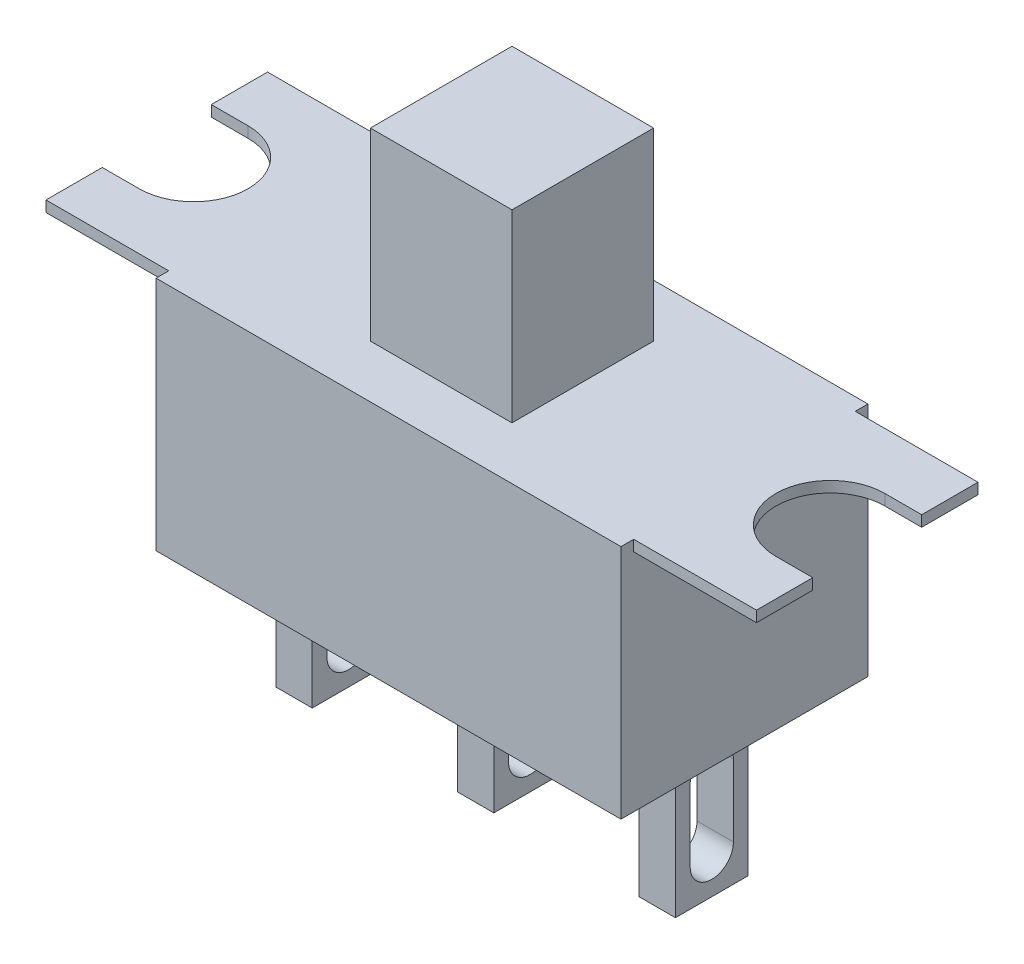
SolidWorks part; units mm, degrees
ref_plane "Front" through (0, 0, 0) normal (0, 0, 1) x (1, 0, 0)
ref_plane "Top" through (0, 0, 0) normal (0, 1, 0) x (1, 0, 0)
ref_plane "Side" through (0, 0, 0) normal (1, 0, 0) x (0, 0, -1)
ref_axis "X_Axis" through (-20.1896, 0, 0) along (1, 0, 0)
ref_axis "Y_Axis" through (0, -14.8261, 0) along (0, 1, 0)
ref_axis "Z_Axis" through (0, 0, -19.842) along (0, 0, 1)
sketch "Sketch1" plane through (0, 0, 0) normal (0, 1, 0) x (1, 0, 0)
  line L1 (6.4, 3.4) -> (-6.4, 3.4)
  line L2 (6.4, 3.4) -> (6.4, -3.4)
  line L3 (6.4, -3.4) -> (-6.4, -3.4)
  line L4 (-6.4, 3.4) -> (-6.4, -3.4)
  line L5 (6.4, 3.4) -> (-6.4, -3.4) construction
  line L6 (6.4, -3.4) -> (-6.4, 3.4) construction
  point P0 (0, 0)
  dimension "D1" = 6.8
  dimension "D2" = 12.8
extrude "Boss-Extrude1" add sketch "Sketch1" along normal blind 6.5
sketch "Sketch2" plane through (0, 6.5, 0) normal (0, 1, 0) x (1, 0, 0)
  line L0 (0, 3.05) -> (0, -3.05) construction
  line L1 (9.78, 3.05) -> (-9.78, 3.05)
  line L2 (9.78, 3.05) -> (9.78, 1.5)
  line L3 (9.78, -3.05) -> (-9.78, -3.05)
  line L4 (-9.78, 3.05) -> (-9.78, 1.5)
  line L5 (9.78, 3.05) -> (-9.78, -3.05) construction
  line L6 (9.78, -3.05) -> (-9.78, 3.05) construction
  line L7 (-8.765, 1.5) -> (-9.78, 1.5)
  line L9 (-9.78, -1.5) -> (-8.765, -1.5)
  line L10 (8.765, 1.5) -> (9.78, 1.5)
  line L12 (9.78, -1.5) -> (8.765, -1.5)
  line L13 (-9.78, -1.5) -> (-9.78, -3.05)
  line L14 (9.78, -1.5) -> (9.78, -3.05)
  arc A0 (-8.765, -1.5) -> (-8.765, 1.5) centre (-8.765, 0) ccw
  arc A1 (8.765, 1.5) -> (8.765, -1.5) centre (8.765, 0) ccw
  point P0 (0, 0)
  point P18 (8.765, 0.2525)
  dimension "D3" = 3
  dimension "D1" = 6.1
  dimension "D2" = 19.56
  dimension "D4" = 17.53
extrude "Boss-Extrude2" add sketch "Sketch2" against normal blind 0.3
sketch "Sketch3" plane through (0, 6.5, 0) normal (0, 1, 0) x (1, 0, 0)
  line L1 (1.95, 1.95) -> (-1.95, 1.95)
  line L2 (1.95, 1.95) -> (1.95, -1.95)
  line L3 (1.95, -1.95) -> (-1.95, -1.95)
  line L4 (-1.95, 1.95) -> (-1.95, -1.95)
  line L5 (1.95, 1.95) -> (-1.95, -1.95) construction
  line L6 (1.95, -1.95) -> (-1.95, 1.95) construction
  point P0 (0, 0)
  dimension "D1" = 3.9
  dimension "D2" = 3.9
extrude "Boss-Extrude3" add sketch "Sketch3" along normal blind 5.08
sketch "Sketch4" plane through (0, 0, 0) normal (0, -1, 0) x (1, 0, 0)
  line L0 (-6.4, 0) -> (6.4, 0) construction
  line L1 (-0.5, 1) -> (0.5, 1)
  line L2 (-0.5, 1) -> (-0.5, -1)
  line L3 (-0.5, -1) -> (0.5, -1)
  line L4 (0.5, 1) -> (0.5, -1)
  line L5 (-0.5, 1) -> (0.5, -1) construction
  line L6 (-0.5, -1) -> (0.5, 1) construction
  line L7 (4.5, 1) -> (5.5, 1)
  line L8 (4.5, 1) -> (4.5, -1)
  line L9 (4.5, -1) -> (5.5, -1)
  line L10 (5.5, 1) -> (5.5, -1)
  line L11 (4.5, 1) -> (5.5, -1) construction
  line L12 (4.5, -1) -> (5.5, 1) construction
  line L13 (-5.5, 1) -> (-4.5, 1)
  line L14 (-5.5, 1) -> (-5.5, -1)
  line L15 (-5.5, -1) -> (-4.5, -1)
  line L16 (-4.5, 1) -> (-4.5, -1)
  line L17 (-5.5, 1) -> (-4.5, -1) construction
  line L18 (-5.5, -1) -> (-4.5, 1) construction
  line L19 (-6.4, -3.4) -> (-6.4, 3.4) construction
  line L20 (6.4, 3.05) -> (6.4, -3.05) construction
  point P0 (0, 0)
  point P6 (5, 0)
  point P11 (-5, 0)
  point P22 (0, 0)
  point P23 (0, 0)
  dimension "D1" = 2
  dimension "D2" = 1
  dimension "D3" = 4
  dimension "D4" = 4
extrude "Boss-Extrude4" add sketch "Sketch4" along normal blind 4
sketch "Sketch5" plane through (5.5, 0, 0) normal (1, 0, 0) x (0, 0, -1)
  line L0 (0, -1.01) -> (0, -2.99) construction
  line L1 (0.595, -1.01) -> (0.595, -2.99)
  line L2 (-0.595, -1.01) -> (-0.595, -2.99)
  line L3 (-1, -2) -> (1, -2) construction
  line L4 (-1, -4) -> (-1, 0) construction
  line L5 (1, -4) -> (1, 0) construction
  arc A0 (0.595, -1.01) -> (-0.595, -1.01) centre (0, -1.01) ccw
  arc A1 (-0.595, -2.99) -> (0.595, -2.99) centre (0, -2.99) ccw
  point P3 (0, -2)
  point P14 (0, 0)
  dimension "D1" = 1.98
  dimension "D2" = 1.19
extrude "Cut-Extrude1" cut sketch "Sketch5" against normal through all
